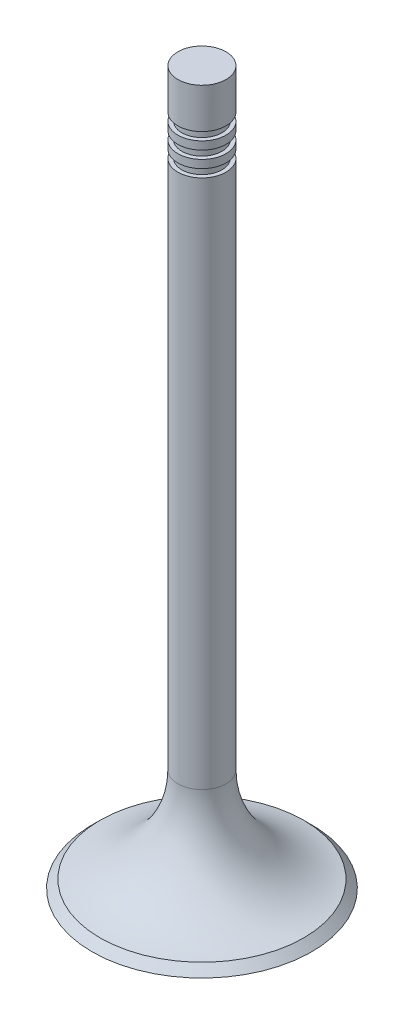
SolidWorks part; units mm, degrees
ref_plane "Front Plane" through (0, 0, 0) normal (0, 0, 1) x (1, 0, 0)
ref_plane "Top Plane" through (0, 0, 0) normal (0, 1, 0) x (1, 0, 0)
ref_plane "Right Plane" through (0, 0, 0) normal (1, 0, 0) x (0, 0, -1)
sketch "Sketch1" plane through (0, 0, 0) normal (0, 1, 0) x (1, 0, 0)
  circle A0 centre (0, 0) radius 13.7
  dimension "D1" = 27.4
extrude "Boss-Extrude1" add sketch "Sketch1" along normal blind 1
chamfer "Chamfer2" distance 1 angle 45 1 edges at (0, 1, 13.7)
sketch "Sketch4" plane through (0, 1, 0) normal (0, 1, 0) x (1, 0, 0)
  circle A0 centre (0, 0) radius 3
  dimension "D1" = 6
extrude "Boss-Extrude2" add sketch "Sketch4" along normal blind 87.8
fillet "Fillet1" radius 12 1 edges at (0, 1, 3)
sketch "Sketch5" plane through (0, 0, 0) normal (0, 0, 1) x (1, 0, 0)
  line L0 (0, 88.8) -> (0, 0) construction
  line L1 (3, 88.8) -> (-3, 88.8) construction
  line L2 (-3, 88.8) -> (-3, 83.8) construction
  line L3 (-3, 88.8) -> (-3, 12.7775) construction
  line L4 (-3, 83.8) -> (-3, 82.8)
  line L5 (-3, 82.8) -> (-3, 81.8)
  line L6 (-3, 81.8) -> (-3, 80.8)
  line L7 (-3, 80.8) -> (-3, 79.8)
  line L8 (-3, 79.8) -> (-3, 78.8)
  line L9 (-3, 78.8) -> (-3, 77.8)
  line L11 (-3, 83.8) -> (-2.5, 83.8)
  line L12 (-3, 83.8) -> (-3, 82.8)
  line L13 (-3, 82.8) -> (-2.5, 82.8)
  line L14 (-2.5, 83.8) -> (-2.5, 82.8)
  line L15 (-3, 81.8) -> (-2.5, 81.8)
  line L16 (-3, 81.8) -> (-3, 80.8)
  line L17 (-3, 80.8) -> (-2.5, 80.8)
  line L18 (-2.5, 81.8) -> (-2.5, 80.8)
  line L19 (-3, 79.8) -> (-2.5, 79.8)
  line L20 (-3, 79.8) -> (-3, 78.8)
  line L21 (-3, 78.8) -> (-2.5, 78.8)
  line L22 (-2.5, 79.8) -> (-2.5, 78.8)
  dimension "D1" = 5
  dimension "D2" = 1
  dimension "D3" = 1
  dimension "D4" = 1
  dimension "D5" = 1
  dimension "D6" = 1
  dimension "D7" = 1
  dimension "D8" = 0.5
revolve "Cut-Revolve1" cut sketch "Sketch5" angle 360 about L0 region at (-2.75, 83.3, 0) region at (-2.75, 79.3, 0) region at (-2.75, 81.3, 0)
